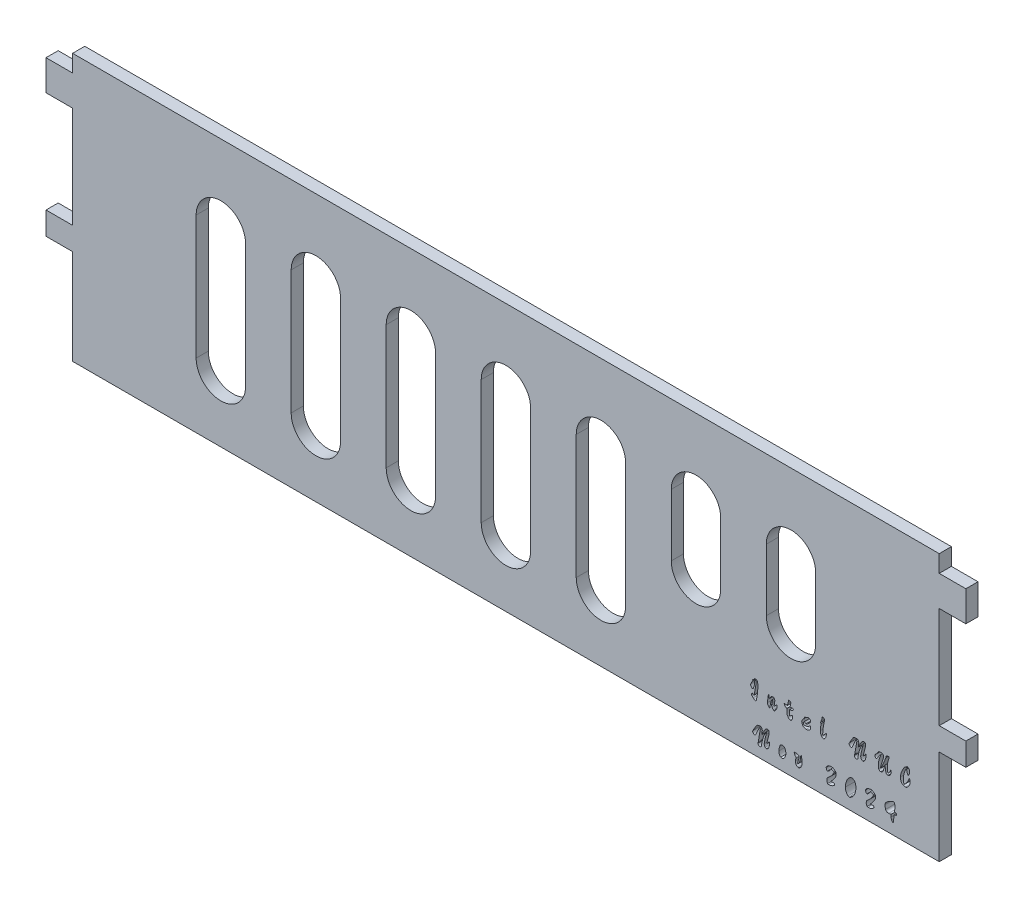
SolidWorks part; units mm, degrees
ref_plane "前视基准面" through (0, 0, 0) normal (0, 0, 1) x (1, 0, 0)
ref_plane "上视基准面" through (0, 0, 0) normal (0, 1, 0) x (1, 0, 0)
ref_plane "右视基准面" through (0, 0, 0) normal (1, 0, 0) x (0, 0, -1)
sketch "草图1" plane through (0, 0, 0) normal (0, 0, 1) x (1, 0, 0)
  line L0 (0, 0) -> (0, 38.8053) construction
  line L11 (0, 0) -> (-51.2518, 0) construction
  line L12 (60.5, 4) -> (-60.5, 4)
  line L13 (-60.5, 4) -> (-60.5, 0)
  line L14 (-60.5, 0) -> (-57, 0)
  line L15 (-57, 0) -> (-57, -16.35) construction
  line L16 (-57, -16.35) -> (57, -16.35)
  line L17 (57, 0) -> (57, -16.35) construction
  line L18 (60.5, 0) -> (57, 0)
  line L19 (60.5, 4) -> (60.5, 0)
  line L20 (-57, -13.35) -> (-60.5, -13.35)
  line L21 (-60.5, -13.35) -> (-60.5, -16.35)
  line L22 (-60.5, -16.35) -> (-57, -16.35)
  line L23 (-57, 0) -> (-57, -13.35)
  line L24 (60.5, -16.35) -> (57, -16.35)
  line L25 (60.5, -13.35) -> (60.5, -16.35)
  line L26 (57, -13.35) -> (60.5, -13.35)
  line L27 (57, 0) -> (57, -13.35)
  line L28 (-60.5, 2) -> (-43.2943, 2) construction
  point P6 (-58.75, 0)
  point P12 (0, -16.35)
  point P15 (0, 4)
  dimension "D1" = 3.5
  dimension "D2" = 4
  dimension "D3" = 114
  dimension "D4" = 15.35
  dimension "D5" = 3
extrude "主体" add sketch "草图1" along normal blind 1.6
ref_plane "旋转轴所在面" through (0, 0, 0.8) normal (0, 0, -1) x (-1, 0, 0)
sketch "旋转轴示意" plane through (0, 0, 0.8) normal (0, 0, -1) x (-1, 0, 0)
  line L0 (-60.5, 2) -> (-97.5011, 2) construction
  line L1 (-60.5, 0) -> (-60.5, 4) construction
  point P4 (-97.5011, 2)
sketch "草图3" plane through (0, 0, 0) normal (0, 0, -1) x (-1, 0, 0)
  line L0 (-57, 4) -> (-57, 6.25)
  line L1 (-60.5, 4) -> (60.5, 4) construction
  line L2 (-57, 6.25) -> (57, 6.25)
  line L3 (57, 6.25) -> (57, 4)
  line L4 (57, 4) -> (-57, 4)
  line L5 (-57, -13.35) -> (-57, 0) construction
  line L6 (57, 0) -> (57, -13.35) construction
  line L7 (-57, -28.85) -> (-57, -16.35)
  line L8 (-57, -16.35) -> (57, -16.35)
  line L9 (57, -16.35) -> (57, -28.85)
  line L10 (57, -28.85) -> (-57, -28.85)
  line L11 (60.5, -16.35) -> (-60.5, -16.35) construction
  dimension "D1" = 2.25
  dimension "D2" = 12.5
extrude "结构补强" add sketch "草图3" against normal up to surface (1.6 mm away) up to face at (0, -6.5083, 1.6)
sketch "草图4" plane through (0, 0, 1.6) normal (0, 0, 1) x (1, 0, 0)
  line L0 (0, -4.05) -> (0, -20.35) construction
  line L3 (3.25, -4.05) -> (3.25, -20.35)
  line L6 (-3.25, -4.05) -> (-3.25, -20.35)
  line L9 (-57, -28.85) -> (57, -28.85) construction
  line L12 (12.5, -4.05) -> (12.5, -20.35) construction
  line L13 (21.75, -4.05) -> (21.75, -12.2)
  line L14 (28.25, -4.05) -> (28.25, -12.2)
  line L15 (15.75, -4.05) -> (15.75, -20.35)
  line L16 (9.25, -4.05) -> (9.25, -20.35)
  line L17 (25, -4.05) -> (25, -20.35) construction
  line L18 (28.25, -4.05) -> (28.25, -20.35) construction
  line L19 (21.75, -4.05) -> (21.75, -20.35) construction
  line L20 (0, -4.05) -> (12.5, -4.05) construction
  line L21 (-12.5, -4.05) -> (-12.5, -20.35) construction
  line L22 (-9.25, -4.05) -> (-9.25, -20.35)
  line L23 (-15.75, -4.05) -> (-15.75, -20.35)
  line L24 (-25, -4.05) -> (-25, -20.35) construction
  line L25 (-21.75, -4.05) -> (-21.75, -20.35)
  line L26 (-28.25, -4.05) -> (-28.25, -20.35)
  line L27 (0, -4.05) -> (-12.5, -4.05) construction
  line L28 (57, -22.6) -> (15.75, -22.6) construction
  line L29 (57, -28.85) -> (57, -16.35) construction
  line L30 (-37.5, -4.05) -> (-37.5, -20.35) construction
  line L31 (-34.25, -4.05) -> (-34.25, -20.35)
  line L32 (-40.75, -4.05) -> (-40.75, -20.35)
  line L33 (40.75, -4.05) -> (40.75, -12.2)
  line L34 (34.25, -4.05) -> (34.25, -12.2)
  line L35 (28.25, -4.05) -> (40.75, -4.05) construction
  arc A8 (3.25, -4.05) -> (-3.25, -4.05) centre (0, -4.05) ccw
  arc A9 (-3.25, -20.35) -> (3.25, -20.35) centre (0, -20.35) ccw
  arc A10 (15.75, -4.05) -> (9.25, -4.05) centre (12.5, -4.05) ccw
  arc A11 (9.25, -20.35) -> (15.75, -20.35) centre (12.5, -20.35) ccw
  arc A12 (28.25, -4.05) -> (21.75, -4.05) centre (25, -4.05) ccw construction
  arc A13 (21.75, -20.35) -> (28.25, -20.35) centre (25, -20.35) ccw construction
  arc A14 (-9.25, -4.05) -> (-15.75, -4.05) centre (-12.5, -4.05) ccw
  arc A15 (-15.75, -20.35) -> (-9.25, -20.35) centre (-12.5, -20.35) ccw
  arc A16 (-21.75, -4.05) -> (-28.25, -4.05) centre (-25, -4.05) ccw
  arc A17 (-28.25, -20.35) -> (-21.75, -20.35) centre (-25, -20.35) ccw
  arc A18 (21.75, -12.2) -> (28.25, -12.2) centre (25, -12.2) ccw
  arc A19 (21.75, -4.05) -> (28.25, -4.05) centre (25, -4.05) cw
  arc A20 (-34.25, -4.05) -> (-40.75, -4.05) centre (-37.5, -4.05) ccw
  arc A21 (-40.75, -20.35) -> (-34.25, -20.35) centre (-37.5, -20.35) ccw
  arc A22 (34.25, -12.2) -> (40.75, -12.2) centre (37.5, -12.2) ccw
  arc A23 (34.25, -4.05) -> (40.75, -4.05) centre (37.5, -4.05) cw
  text T0 "Intel NUC  \r\nNov 2024   " font "钟齐志莽行书" height 2.5
  point P3 (0, -12.2)
  point P13 (12.5, -12.2)
  point P20 (25, -12.2)
  point P29 (-12.5, -12.2)
  point P37 (-25, -12.2)
  point P56 (-37.5, -12.2)
  dimension "D3" = 3.25
  dimension "D2" = 8.5
  dimension "D4" = 12.5
  dimension "D1" = 4.05
  dimension "D5" = 12.5
  dimension "D8" = 12.5
  dimension "D6" = 3
  dimension "D7" = 4
extrude "切除-拉伸1" cut sketch "草图4" against normal through all
